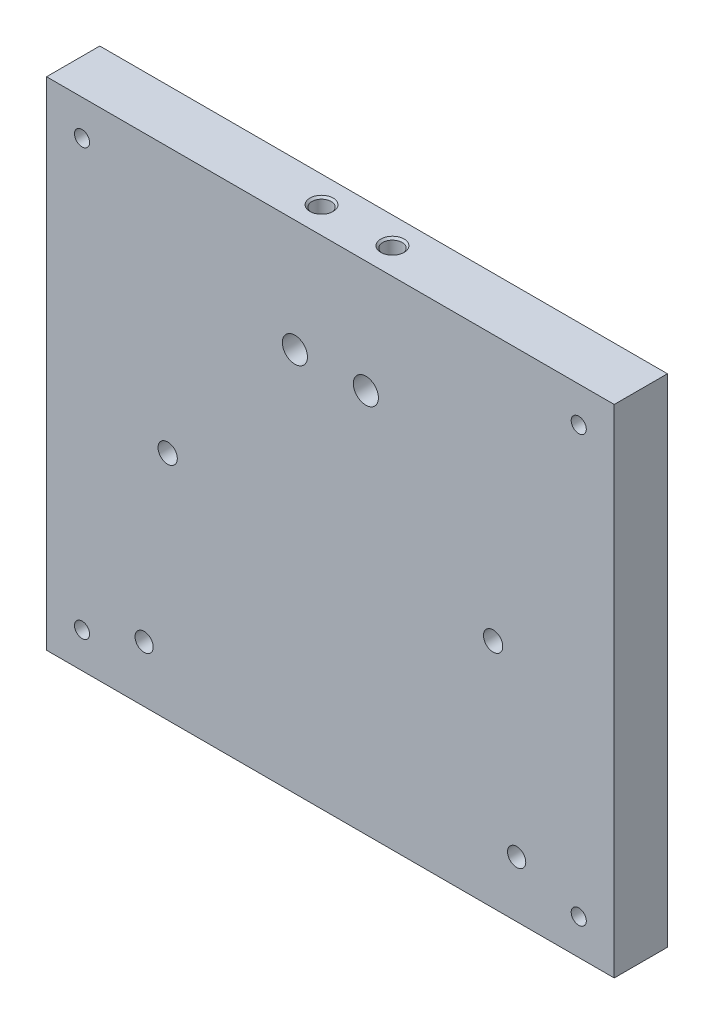
SolidWorks part; units mm, degrees
material "6061-T6 (SS)"
ref_plane "Front Plane" through (0, 0, 0) normal (0, 0, 1) x (1, 0, 0)
ref_plane "Top Plane" through (0, 0, 0) normal (0, 1, 0) x (1, 0, 0)
ref_plane "Right Plane" through (0, 0, 0) normal (1, 0, 0) x (0, 0, -1)
sketch "Sketch1" plane through (0, 0, 0) normal (0, 0, 1) x (1, 0, 0)
  line L1 (0, 0) -> (-101.6, 0)
  line L2 (0, 0) -> (0, 88.9)
  line L3 (0, 88.9) -> (-101.6, 88.9)
  line L4 (-101.6, 0) -> (-101.6, 88.9)
  dimension "D1" = 101.6
  dimension "D2" = 88.9
extrude "Boss-Extrude1" add sketch "Sketch1" along normal blind 9.525
sketch "Sketch5" plane through (0, 88.9, 0) normal (0, 1, 0) x (1, 0, 0)
  line L0 (-101.6, -4.7625) -> (0, -4.7625) construction
  line L1 (-101.6, -9.525) -> (-101.6, 0) construction
  line L2 (0, -9.525) -> (0, 0) construction
  line L3 (-57.15, -4.7625) -> (-44.45, -4.7625)
  point P8 (-50.8, -4.7625)
  dimension "D1" = 12.7
hole_wizard "#8-32 Tapped Hole1" positions "Sketch6" profile "Sketch8" tap size "#8-32" standard "ANSI Inch"
sketch "Sketch6" plane through (0, 88.9, 0) normal (0, 1, 0) x (1, 0, 0)
  point P0 (-44.45, -4.7625)
  point P3 (-57.15, -4.7625)
sketch "Sketch8" plane through (-44.45, 88.9, 4.7625) normal (1, 0, 0) x (0, 0, 1)
  line L0 (0, 0) -> (0, 20.0878)
  line L1 (0, 20.0878) -> (1.7272, 19.05)
  line L2 (1.7272, 19.05) -> (1.7272, 0.3556)
  line L3 (1.7272, 0.3556) -> (2.0828, 0)
  line L5 (2.0828, 0) -> (0, 0)
  line L6 (-1.7272, 0.3556) -> (-2.0828, 0) construction
  line L10 (0, 20.0878) -> (-1.7272, 19.05) construction
  line L11 (0, -6.35) -> (0, 107.95) construction
  dimension "Tap Drill Dia." = 3.4544
  dimension "Tap Drill Depth" = 19.05
  dimension "Near C'Sink Dia." = 4.1656
  dimension "Near C'Sink Angle" = 90
  dimension "Drill Angle" = 118
cosmetic thread "Hole Thread1" parameters "D1"=12.7, "D2"=4.1656
cosmetic thread "Hole Thread2" parameters "D1"=12.7, "D2"=4.1656
hole_wizard "#8 Clearance Hole2" positions "Sketch11" profile "Sketch12" hole size "#8" standard "ANSI Inch"
sketch "Sketch11" plane through (0, 0, 9.525) normal (0, 0, 1) x (1, 0, 0)
  line L0 (-44.45, 68.8122) -> (-42.7228, 69.85) construction
  line L1 (-57.15, 68.8122) -> (-55.4228, 69.85) construction
  line L2 (-44.45, 68.8122) -> (-42.7228, 69.85)
  line L3 (-57.15, 68.8122) -> (-55.4228, 69.85)
  point P1 (-44.45, 68.8122)
  point P3 (-57.15, 68.8122)
sketch "Sketch12" plane through (-44.45, 68.8122, 9.525) normal (1, 0, 0) x (0, -1, 0)
  line L0 (0, 0) -> (0, 26.7507)
  line L1 (0, 26.7507) -> (2.2479, 25.4)
  line L2 (2.2479, 25.4) -> (2.2479, 0)
  line L5 (2.2479, 0) -> (0, 0)
  line L10 (0, 26.7507) -> (-2.2479, 25.4) construction
  line L11 (0, -6.35) -> (0, 107.95) construction
  dimension "Hole Dia." = 4.4958
  dimension "Hole Depth" = 25.4
  dimension "Drill Angle" = 118
sketch "Sketch13" plane through (0, 0, 9.525) normal (0, 0, 1) x (1, 0, 0)
  line L8 (-6.35, 6.35) -> (-6.35, 82.55)
  line L9 (-6.35, 82.55) -> (-95.25, 82.55)
  line L10 (-95.25, 82.55) -> (-95.25, 6.35)
  line L11 (-95.25, 6.35) -> (-6.35, 6.35)
  line L12 (-6.35, 6.35) -> (-6.35, 82.55)
  line L13 (-6.35, 82.55) -> (-95.25, 82.55)
  line L14 (-95.25, 82.55) -> (-95.25, 6.35)
  line L15 (-95.25, 6.35) -> (-6.35, 6.35)
  dimension "D1" = 6.35
hole_wizard "#6-32 Tapped Hole1" positions "Sketch14" profile "Sketch16" tap size "#6-32" standard "ANSI Inch" end condition through all
sketch "Sketch14" plane through (0, 0, 9.525) normal (0, 0, 1) x (1, 0, 0)
  point P0 (-95.25, 6.35)
  point P3 (-95.25, 82.55)
  point P6 (-6.35, 6.35)
  point P9 (-6.35, 82.55)
sketch "Sketch16" plane through (-95.25, 6.35, 9.525) normal (1, 0, 0) x (0, -1, 0)
  line L0 (0, 0) -> (0, 9.525)
  line L1 (0, 9.525) -> (1.3525, 9.525)
  line L2 (1.3525, 9.525) -> (1.3525, 0)
  line L5 (1.3525, 0) -> (0, 0)
  line L11 (0, -6.35) -> (0, 107.95) construction
  dimension "Thru Tap Drill Dia." = 2.7051
  dimension "Thru Tap Drill Depth" = 9.525
cosmetic thread "Hole Thread3" parameters "D2"=3.5052
cosmetic thread "Hole Thread4" parameters "D2"=3.5052
cosmetic thread "Hole Thread5" parameters "D2"=3.5052
cosmetic thread "Hole Thread6" parameters "D2"=3.5052
sketch "Sketch17" plane through (0, 0, 9.525) normal (0, 0, 1) x (1, 0, 0)
  line L0 (-82.55, 12.7) -> (-19.05, 12.7)
  line L1 (-82.55, 12.7) -> (-101.6, 12.7)
  line L2 (-101.6, 88.9) -> (-101.6, 0) construction
  line L3 (-19.05, 12.7) -> (0, 12.7)
  line L4 (0, 0) -> (0, 88.9) construction
  line L5 (-101.6, 0) -> (0, 0) construction
  dimension "D1" = 63.5
  dimension "D2" = 12.7
hole_wizard "#4 Clearance Hole1" positions "Sketch18" profile "Sketch20" hole size "#4" standard "ANSI Inch" end condition up to next
sketch "Sketch18" plane through (0, 0, 9.525) normal (0, 0, 1) x (1, 0, 0)
  point P6 (-17.4625, 10.033)
  point P9 (-84.1375, 10.033)
sketch "Sketch20" plane through (-17.4625, 10.033, 9.525) normal (1, 0, 0) x (0, -1, 0)
  line L0 (0, 0) -> (0, 9.525)
  line L1 (0, 9.525) -> (1.6319, 9.525)
  line L2 (1.6319, 9.525) -> (1.6319, 0)
  line L5 (1.6319, 0) -> (0, 0)
  line L11 (0, -6.35) -> (0, 107.95) construction
  dimension "Thru Hole Dia." = 3.2639
  dimension "Thru Hole Depth" = 9.525
hole_wizard "#8-32 Tapped Hole2" positions "Sketch21" profile "Sketch22" tap size "#8-32" standard "ANSI Inch" end condition through all
sketch "Sketch21" plane through (0, 0, 0) normal (0, 0, -1) x (-1, 0, 0)
  point P6 (79.925, 41.402)
  point P9 (21.675, 41.402)
sketch "Sketch22" plane through (-79.925, 41.402, 0) normal (1, 0, 0) x (0, 1, 0)
  line L0 (0, 0) -> (0, 9.525)
  line L1 (0, 9.525) -> (1.7272, 9.525)
  line L2 (1.7272, 9.525) -> (1.7272, 0)
  line L5 (1.7272, 0) -> (0, 0)
  line L11 (0, -6.35) -> (0, 107.95) construction
  dimension "Thru Tap Drill Dia." = 3.4544
  dimension "Thru Tap Drill Depth" = 9.525
cosmetic thread "Hole Thread7" parameters "D2"=4.1656
cosmetic thread "Hole Thread8" parameters "D2"=4.1656
